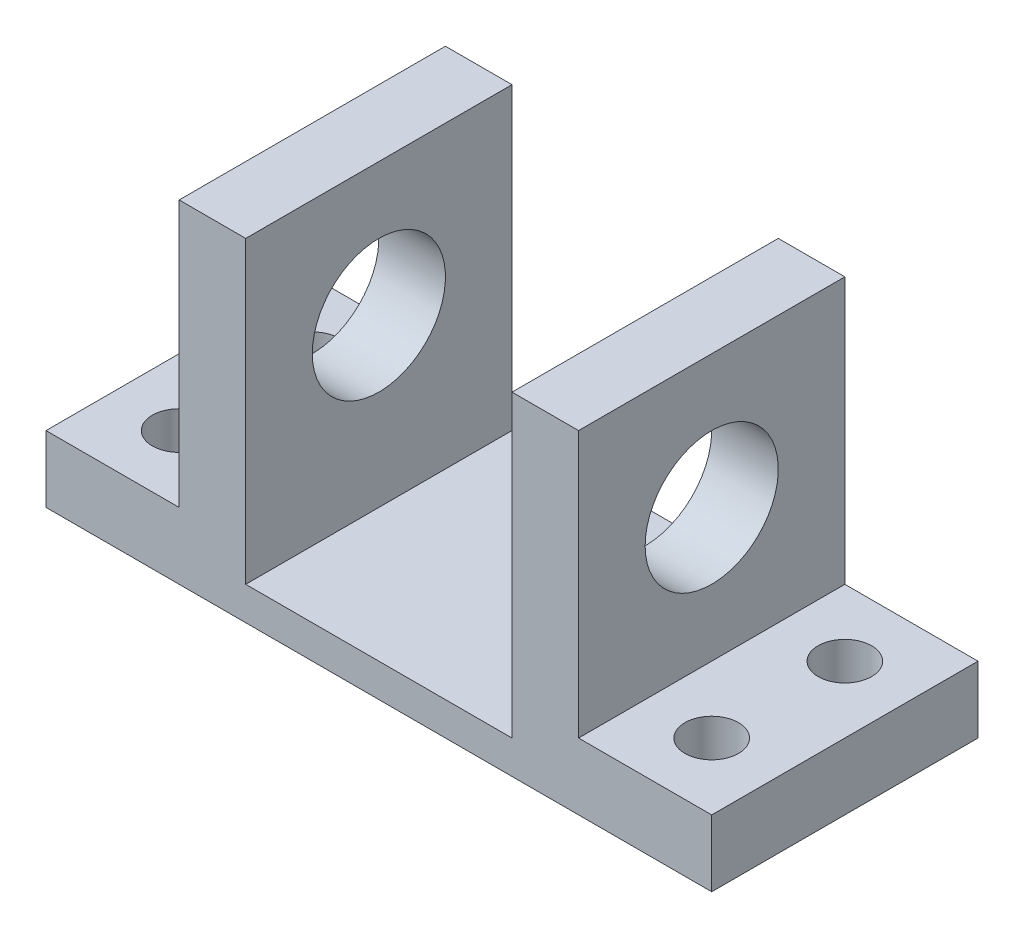
SolidWorks part; units mm, degrees
ref_plane "Front Plane" through (0, 0, 0) normal (0, 0, 1) x (1, 0, 0)
ref_plane "Top Plane" through (0, 0, 0) normal (0, 1, 0) x (1, 0, 0)
ref_plane "Right Plane" through (0, 0, 0) normal (1, 0, 0) x (0, 0, -1)
sketch "Sketch2" plane through (0, 0, 0) normal (0, 1, 0) x (1, 0, 0)
  line L0 (6.35, 0) -> (6.35, 25.4)
  line L1 (0, 0) -> (38.1, 0)
  line L2 (0, 0) -> (0, 25.4)
  line L3 (0, 25.4) -> (38.1, 25.4)
  line L4 (38.1, 0) -> (38.1, 25.4)
  line L5 (31.75, 0) -> (31.75, 25.4)
  dimension "D1" = 38.1
  dimension "D2" = 25.4
  dimension "D3" = 6.35
  dimension "D4" = 6.35
extrude "Boss-Extrude1" add sketch "Sketch2" along normal blind 31.75 contours L3 L2 L1 L0 | L5 L1 L4 L3 region at (3.175, 0, -12.7) region at (34.925, 0, -12.7)
extrude "Boss-Extrude2" add sketch "Sketch2<3>" along normal blind 3.175 contours L1 L5 L3 L0 region at (19.05, 0, -12.7)
sketch "Sketch2<3>" plane through (0, 0, 0) normal (0, 1, 0) x (1, 0, 0) same geometry as "Sketch2"
sketch "Sketch3" plane through (0, 0, 0) normal (-1, 0, 0) x (0, 0, 1)
  line L0 (-12.7, 31.75) -> (-12.7, 19.05) construction
  line L1 (0, 31.75) -> (-25.4, 31.75) construction
  circle A0 centre (-12.7, 19.05) radius 6.35
  dimension "D2" = 12.7
  dimension "D1" = 12.7
extrude "Cut-Extrude1" cut sketch "Sketch3" against normal through all
sketch "Sketch4" plane through (0, 0, 0) normal (-1, 0, 0) x (0, 0, 1)
  line L0 (0, 31.75) -> (0, 0) construction
  line L1 (-25.4, 0) -> (0, 0)
  line L2 (-25.4, 0) -> (-25.4, 6.35)
  line L3 (-25.4, 6.35) -> (0, 6.35)
  line L4 (0, 0) -> (0, 6.35)
  dimension "D1" = 6.35
extrude "Boss-Extrude3" add sketch "Sketch4" along normal blind 12.7
sketch "Sketch9" plane through (38.1, 0, 0) normal (1, 0, 0) x (0, 0, -1)
  line L0 (25.4, 31.75) -> (25.4, 0) construction
  line L1 (0, 0) -> (25.4, 0)
  line L2 (0, 0) -> (0, 6.35)
  line L3 (0, 6.35) -> (25.4, 6.35)
  line L4 (25.4, 0) -> (25.4, 6.35)
  dimension "D1" = 6.35
extrude "Boss-Extrude5" add sketch "Sketch9" along normal blind 12.7
sketch "Sketch10" plane through (0, 6.35, 0) normal (0, 1, 0) x (1, 0, 0)
  line L0 (-12.7, 19.05) -> (50.8, 19.05) construction
  line L1 (-12.7, 0) -> (-12.7, 25.4) construction
  line L2 (50.8, 25.4) -> (50.8, 0) construction
  line L3 (-12.7, 6.35) -> (50.8, 6.35) construction
  line L4 (-12.7, 0) -> (0, 0) construction
  line L5 (-12.7, 25.4) -> (0, 25.4) construction
  dimension "D1" = 6.35
  dimension "D2" = 6.35
hole_wizard "1/4-20 Tapped Hole3" positions "3DSketch3" profile "Sketch11" tap size "1/4-20" standard "ANSI Inch"
sketch3d "3DSketch3"
  line L0 (-12.7, 6.35, -19.05) -> (50.8, 6.35, -19.05) construction
  line L1 (-12.7, 6.35, -6.35) -> (50.8, 6.35, -6.35) construction
  point P0 (-6.35, 6.35, -19.05)
  point P4 (-6.35, 6.35, -6.35)
  point P8 (44.45, 6.35, -6.35)
  point P10 (44.45, 6.35, -19.05)
  dimension "D1" = 6.35
  dimension "D2" = 6.35
  dimension "D3" = 6.35
  dimension "D4" = 6.35
sketch "Sketch11" plane through (-6.35, 6.35, -19.05) normal (1, 0, 0) x (0, 0, 1)
  line L0 (0, 0) -> (0, 20.5838)
  line L1 (0, 20.5838) -> (2.5527, 19.05)
  line L2 (2.5527, 19.05) -> (2.5527, 0)
  line L5 (2.5527, 0) -> (0, 0)
  line L10 (0, 20.5838) -> (-2.5527, 19.05) construction
  line L11 (0, -6.35) -> (0, 107.95) construction
  dimension "Tap Drill Dia." = 5.1054
  dimension "Tap Drill Depth" = 19.05
  dimension "Drill Angle" = 118
cosmetic thread "Hole Thread13" parameters "D1"=6.35, "D2"=6.35
cosmetic thread "Hole Thread14" parameters "D1"=6.35, "D2"=6.35
cosmetic thread "Hole Thread15" parameters "D1"=6.35, "D2"=6.35
cosmetic thread "Hole Thread16" parameters "D1"=6.35, "D2"=6.35
